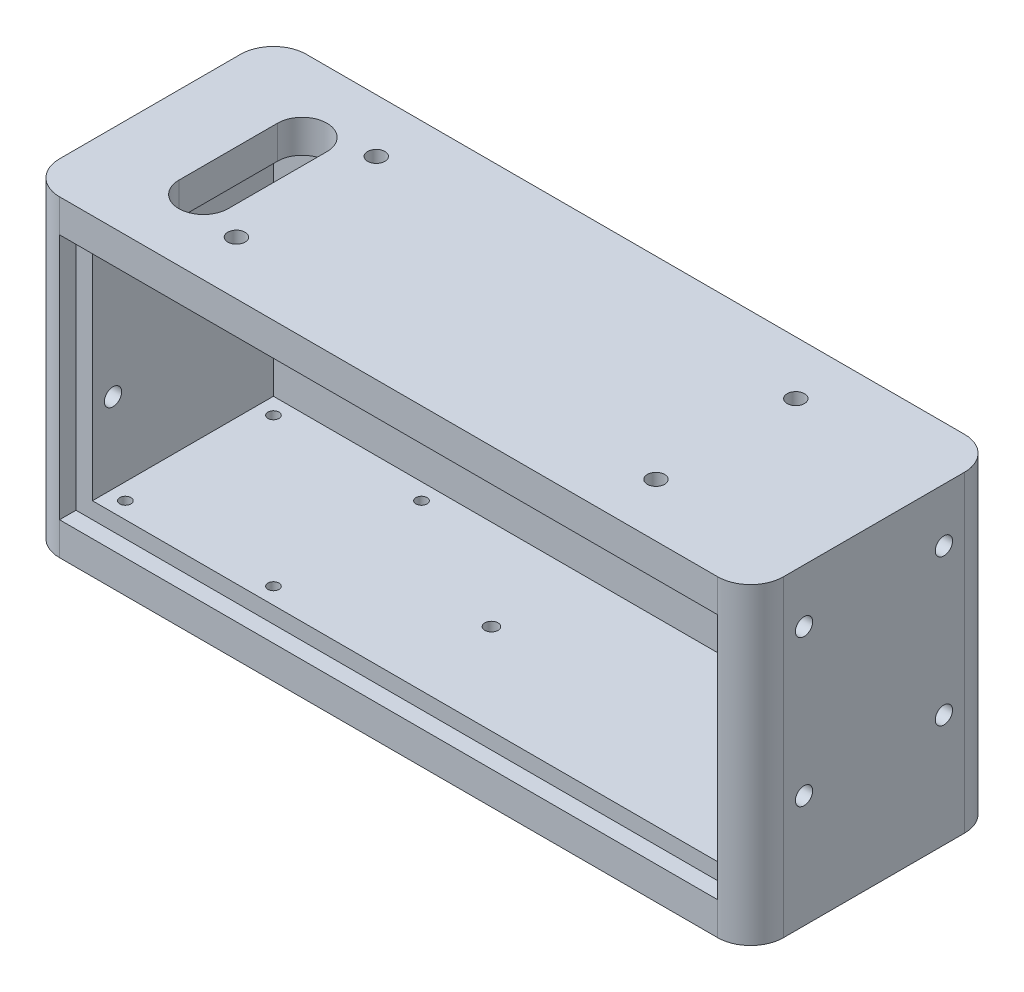
SolidWorks part; units mm, degrees
ref_plane "前视基准面" through (0, 0, 0) normal (0, 0, 1) x (1, 0, 0)
ref_plane "上视基准面" through (0, 0, 0) normal (0, 1, 0) x (1, 0, 0)
ref_plane "右视基准面" through (0, 0, 0) normal (1, 0, 0) x (0, 0, -1)
other "Configuration Table"
sketch "草图1" plane through (0, 0, 0) normal (0, 1, 0) x (1, 0, 0)
  line L1 (88, -30) -> (-88, -30)
  line L2 (88, -30) -> (88, 30)
  line L3 (88, 30) -> (-88, 30)
  line L4 (-88, -30) -> (-88, 30)
  line L5 (88, -30) -> (-88, 30) construction
  line L6 (88, 30) -> (-88, -30) construction
  point P0 (0, 0)
  dimension "D1" = 60
  dimension "D2" = 176
extrude "凸台-拉伸1" add sketch "草图1" along normal blind 76
sketch "草图3" plane through (0, 0, 30) normal (0, 0, 1) x (1, 0, 0)
  line L0 (-88, 0) -> (88, 0) construction
  line L1 (80, 8) -> (-80, 8)
  line L2 (80, 8) -> (80, 68)
  line L3 (80, 68) -> (-80, 68)
  line L4 (-80, 8) -> (-80, 68)
  line L5 (80, 8) -> (-80, 68) construction
  line L6 (80, 68) -> (-80, 8) construction
  line L7 (-88, 76) -> (-88, 0) construction
  line L8 (88, 76) -> (88, 0) construction
  line L9 (-88, 76) -> (88, 76) construction
  point P0 (0, 38)
  dimension "D1" = 8
  dimension "D2" = 8
  dimension "D3" = 8
  dimension "D4" = 8
extrude "切除-拉伸1" cut sketch "草图3" against normal blind 52
fillet "圆角1" radius 8 4 edges at (-88, 38, -30) (88, 38, -30) (88, 38, 30) (-88, 38, 30)
sketch "草图4" plane through (-88, 0, 0) normal (-1, 0, 0) x (0, 0, 1)
  line L5 (-22, 76) -> (22, 76) construction
  line L9 (17, 27.4) -> (-17, 27.4) construction
  line L10 (17, 27.4) -> (17, 63) construction
  line L11 (17, 63) -> (-17, 63) construction
  line L13 (-17, 27.4) -> (-17, 63) construction
  line L14 (17, 27.4) -> (-17, 63) construction
  line L15 (17, 63) -> (-17, 27.4) construction
  line L18 (30, 68) -> (30, 8) construction
  line L19 (-30, 0) -> (-30, 76) construction
  line L22 (-17, 45.2) -> (17, 45.2) construction
  line L23 (0, 63) -> (0, 27.4) construction
  circle A8 centre (-17, 63) radius 2.1
  circle A9 centre (17, 63) radius 2.1
  circle A10 centre (17, 27.4) radius 2.1
  circle A11 centre (-17, 27.4) radius 2.1
  point P0 (0, 45.2)
  dimension "D5" = 4.2
  dimension "D1" = 13
  dimension "D2" = 13
  dimension "D3" = 13
  dimension "D4" = 35.6
extrude "切除-拉伸2" cut sketch "草图4" against normal through all
sketch "草图5" plane through (0, 8, 0) normal (0, 1, 0) x (1, 0, 0)
  line L0 (-88, -30) -> (-88, 30) construction
  line L1 (-40, -18) -> (-76, -18) construction
  line L2 (-40, -18) -> (-40, 18) construction
  line L3 (-40, 18) -> (-76, 18) construction
  line L4 (-76, -18) -> (-76, 18) construction
  line L5 (-40, -18) -> (-76, 18) construction
  line L6 (-40, 18) -> (-76, -18) construction
  line L8 (-76, 0) -> (-40, 0) construction
  line L9 (-58, -18) -> (-58, 18) construction
  circle A0 centre (-76, 18) radius 1.35
  circle A1 centre (-40, 18) radius 1.35
  circle A2 centre (-40, -18) radius 1.35
  circle A3 centre (-76, -18) radius 1.35
  point P0 (-58, 0)
  dimension "D4" = 2.7
  dimension "D1" = 12
  dimension "D2" = 36
  dimension "D3" = 36
extrude "切除-拉伸3" cut sketch "草图5" against normal through all
sketch "草图6" plane through (0, 76, 0) normal (0, 1, 0) x (1, 0, 0)
  line L0 (88, -22) -> (88, 22) construction
  line L1 (52, -17) -> (-50, -17) construction
  line L2 (52, -17) -> (52, 17) construction
  line L3 (52, 17) -> (-50, 17) construction
  line L4 (-50, -17) -> (-50, 17) construction
  line L5 (52, -17) -> (-50, 17) construction
  line L6 (52, 17) -> (-50, -17) construction
  line L7 (-80, -30) -> (80, -30) construction
  line L8 (1, 17) -> (1, -17) construction
  line L9 (-50, 0) -> (52, 0) construction
  line L10 (80, 30) -> (-80, 30) construction
  line L11 (-63, -12) -> (-63, 12) construction
  line L12 (-69, -12) -> (-69, 12)
  line L13 (-57, -12) -> (-57, 12)
  circle A0 centre (-50, 17) radius 2.1
  circle A1 centre (52, 17) radius 2.1
  circle A2 centre (52, -17) radius 2.1
  circle A3 centre (-50, -17) radius 2.1
  arc A4 (-69, -12) -> (-57, -12) centre (-63, -12) ccw
  arc A5 (-57, 12) -> (-69, 12) centre (-63, 12) ccw
  point P0 (1, 0)
  point P20 (-63, 0)
  point P29 (-63, 18)
  point P30 (-63, -18)
  dimension "D4" = 4.2
  dimension "D1" = 36
  dimension "D2" = 34
  dimension "D3" = 102
  dimension "D5" = 13
  dimension "D6" = 12
  dimension "D7" = 12
  dimension "D8" = 12
extrude "切除-拉伸4" cut sketch "草图6" against normal up to surface (8 mm away) up to face at (0, 68, 4)
sketch "草图7" plane through (0, 8, 0) normal (0, 1, 0) x (1, 0, 0)
  line L0 (70, 16.5) -> (70, -16.5) construction
  line L2 (88, -22) -> (88, 22) construction
  circle A0 centre (70, 16.5) radius 1.6
  circle A1 centre (70, -16.5) radius 1.6
  circle A2 centre (-5, 0) radius 1.6
  point P6 (70, 0)
  dimension "D1" = 3.2
  dimension "D2" = 3.2
  dimension "D3" = 3.2
  dimension "D4" = 33
  dimension "D5" = 75
  dimension "D6" = 18
extrude "切除-拉伸5" cut sketch "草图7" against normal through all
sketch "草图8" plane through (0, 0, 0) normal (0, -1, 0) x (1, 0, 0)
  line L0 (-58, 18) -> (-58, -18) construction
  line L3 (-76, 0) -> (-40, 0) construction
  circle A0 centre (-76, 18) radius 2.5
  circle A1 centre (-40, 18) radius 2.5
  circle A2 centre (-40, -18) radius 2.5
  circle A3 centre (-76, -18) radius 2.5
  circle A4 centre (-5, 0) radius 3
  circle A5 centre (70, 16.5) radius 3
  circle A6 centre (70, -16.5) radius 3
  dimension "D1" = 5
  dimension "D2" = 6
  dimension "D3" = 6
  dimension "D4" = 6
extrude "切除-拉伸6" cut sketch "草图8" against normal blind 4
sketch "草图9" plane through (-88, 0, 0) normal (-1, 0, 0) x (0, 0, 1)
  line L0 (30, 76) -> (22, 76) construction
  line L1 (22, 72) -> (26, 72)
  line L2 (22, 72) -> (22, 4)
  line L3 (22, 4) -> (26, 4)
  line L4 (26, 72) -> (26, 4)
  line L5 (22, 0) -> (30, 0) construction
  line L6 (30, 68) -> (30, 8) construction
  dimension "D1" = 4
  dimension "D2" = 4
  dimension "D3" = 4
  dimension "D4" = 4
extrude "切除-拉伸7" cut sketch "草图9" against normal blind 172
sketch "草图10" plane through (0, 0, -30) normal (0, 0, -1) x (-1, 0, 0)
  line L0 (-80, 27) -> (80, 27) construction
  line L1 (-80, 76) -> (-80, 0) construction
  line L2 (80, 0) -> (80, 76) construction
  line L3 (-80, 0) -> (80, 0) construction
  text T0 "XUANWU" font "Georgia" height 22
  dimension "D1" = 27
extrude "切除-拉伸8" cut sketch "草图10" against normal blind 2
